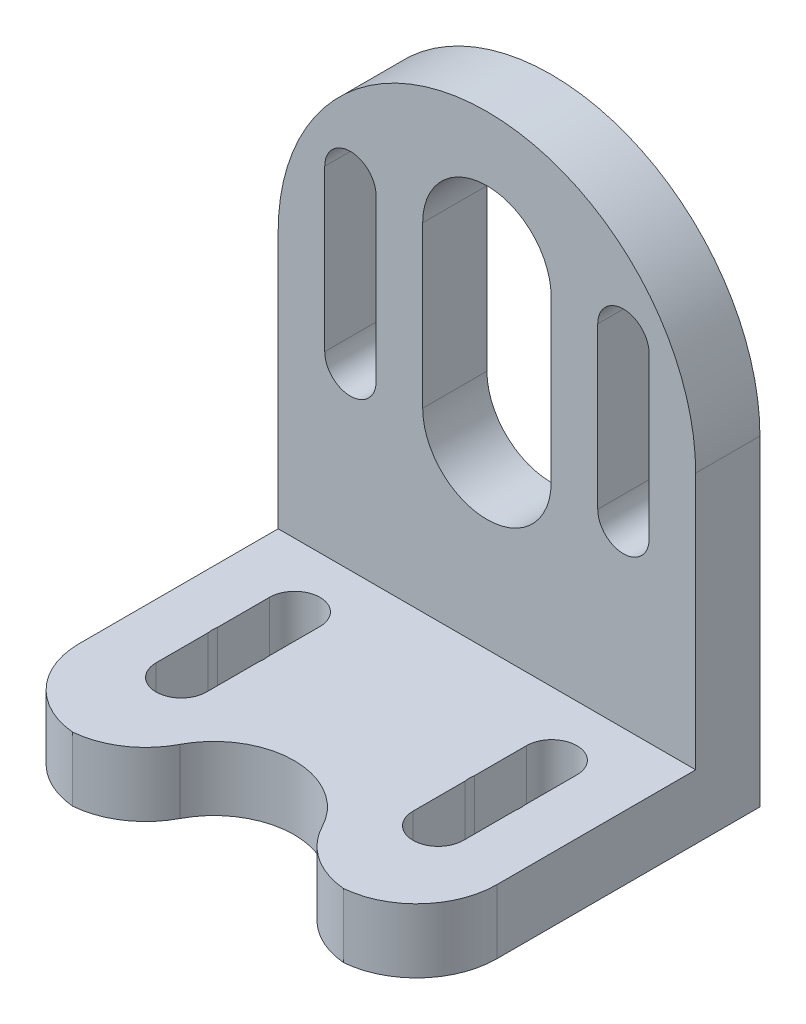
SolidWorks part; units mm, degrees
ref_plane "Front Plane" through (0, 0, 0) normal (0, 0, 1) x (1, 0, 0)
ref_plane "Top Plane" through (0, 0, 0) normal (0, 1, 0) x (1, 0, 0)
ref_plane "Right Plane" through (0, 0, 0) normal (1, 0, 0) x (0, 0, -1)
sketch "Sketch1" plane through (0, 0, 0) normal (0, 0, 1) x (1, 0, 0)
  line L0 (0, 23) -> (0, -10) construction
  line L1 (13, -10) -> (-13, -10)
  line L2 (13, -10) -> (13, 10)
  line L4 (-13, -10) -> (-13, 10)
  line L5 (13, -10) -> (-13, 10) construction
  line L6 (13, 10) -> (-13, -10) construction
  arc A0 (-13, 10) -> (13, 10) centre (0, 10) cw
  circle A1 centre (0, 10) radius 4
  circle A2 centre (-8.5, 10) radius 1.6
  circle A3 centre (8.5, 10) radius 1.6
  point P0 (0, 0)
  dimension "D3" = 13
  dimension "D4" = 8
  dimension "D5" = 3.2
  dimension "D1" = 26
  dimension "D2" = 20
  dimension "D6" = 8.5
extrude "Boss-Extrude1" add sketch "Sketch1" along normal blind 4
sketch "Sketch2" plane through (0, 0, 4) normal (0, 0, 1) x (1, 0, 0)
  line L0 (13, -10) -> (13, 10) construction
  line L1 (-13, -10) -> (13, -10)
  line L2 (-13, -10) -> (-13, -6)
  line L3 (-13, -6) -> (13, -6)
  line L4 (13, -10) -> (13, -6)
  dimension "D1" = 4
extrude "Boss-Extrude2" add sketch "Sketch2" along normal blind 33
sketch "Sketch3" plane through (0, -10, 0) normal (0, -1, 0) x (1, 0, 0)
  line L0 (0, 37) -> (0, 0) construction
  line L1 (-13, 37) -> (13, 37) construction
  line L2 (-13, 18.5) -> (13, 18.5) construction
  line L3 (-13, 37) -> (-13, 0) construction
  line L4 (13, 37) -> (13, 0) construction
  circle A0 centre (0, 21) radius 5
  circle A1 centre (-8, 25.5) radius 1.6
  circle A2 centre (8, 25.5) radius 1.6
  circle A3 centre (8, 11.5) radius 1.6
  circle A4 centre (-8, 11.5) radius 1.6
  dimension "D2" = 10
  dimension "D3" = 3.2
  dimension "D1" = 16
  dimension "D4" = 8
  dimension "D5" = 14
extrude "Cut-Extrude1" cut sketch "Sketch3" against normal blind 33
sketch "Sketch4" plane through (0, 0, 4) normal (0, 0, 1) x (1, 0, 0)
  line L0 (-8.5, 5) -> (-8.5, 15) construction
  line L1 (-10.1, 5) -> (-10.1, 15)
  line L2 (-6.9, 5) -> (-6.9, 15)
  line L3 (0, 23) -> (0, -0.4372) construction
  line L4 (8.5, 5) -> (8.5, 15) construction
  line L5 (10.1, 5) -> (10.1, 15)
  line L6 (6.9, 5) -> (6.9, 15)
  arc A0 (-10.1, 5) -> (-6.9, 5) centre (-8.5, 5) ccw
  arc A1 (-6.9, 15) -> (-10.1, 15) centre (-8.5, 15) ccw
  arc A2 (13, 10) -> (-13, 10) centre (0, 10) ccw construction
  arc A3 (10.1, 5) -> (6.9, 5) centre (8.5, 5) cw
  arc A4 (6.9, 15) -> (10.1, 15) centre (8.5, 15) cw
  point P2 (-8.5, 10)
  point P17 (8.5, 10)
  dimension "D1" = 1.6
  dimension "D2" = 10
extrude "Cut-Extrude2" cut sketch "Sketch4" against normal blind 33
sketch "Sketch5" plane through (0, 0, 4) normal (0, 0, 1) x (1, 0, 0)
  line L0 (-10.1, 15) -> (-10.1, 5) construction
  line L1 (6.9, 15) -> (6.9, 5) construction
  line L2 (4, 10) -> (-10.1, 10) construction
  circle A0 centre (-8.5, 10) radius 1.6
  circle A1 centre (8.5, 10) radius 1.6
  circle A2 centre (0, 10) radius 4 construction
  dimension "D1" = 3.2
  dimension "D2" = 3.2
sketch "Sketch6" plane through (0, -6, 0) normal (0, 1, 0) x (1, 0, 0)
  line L0 (8, -15.0323) -> (8, -7.9677) construction
  line L1 (6.4265, -15.0323) -> (6.4265, -7.9677)
  line L2 (9.5735, -15.0323) -> (9.5735, -7.9677)
  line L3 (0, -4) -> (0, -16) construction
  line L4 (4, -4) -> (-10.1, -4) construction
  line L5 (-8, -15.0323) -> (-8, -7.9677) construction
  line L6 (-6.4265, -15.0323) -> (-6.4265, -7.9677)
  line L7 (-9.5735, -15.0323) -> (-9.5735, -7.9677)
  arc A0 (6.4265, -15.0323) -> (9.5735, -15.0323) centre (8, -15.0323) ccw
  arc A1 (9.5735, -7.9677) -> (6.4265, -7.9677) centre (8, -7.9677) ccw
  circle A2 centre (0, -21) radius 5 construction
  arc A3 (-6.4265, -15.0323) -> (-9.5735, -15.0323) centre (-8, -15.0323) cw
  arc A4 (-9.5735, -7.9677) -> (-6.4265, -7.9677) centre (-8, -7.9677) cw
  point P2 (8, -11.5)
  point P17 (-8, -11.5)
extrude "Cut-Extrude3" cut sketch "Sketch6" against normal blind 5
sketch "Sketch7" plane through (0, -6, 0) normal (0, 1, 0) x (1, 0, 0)
  line L0 (13, -37) -> (13, -4) construction
  line L1 (-13, -37) -> (13, -37)
  line L2 (-13, -37) -> (-13, -21.3817)
  line L3 (-13, -21.3817) -> (13, -21.3817)
  line L4 (13, -37) -> (13, -21.3817)
extrude "Cut-Extrude4" cut sketch "Sketch7" against normal blind 5
fillet "Fillet1" radius 5 4 edges at (-13, -8, 21.3817) (13, -8, 21.3817) (4.9854, -8, 21.3817) (-4.9854, -8, 21.3817)
sketch "Sketch8" plane through (0, 0, 0) normal (0, 0, -1) x (-1, 0, 0)
  line L0 (0, 5) -> (0, 15) construction
  line L1 (-4, 5) -> (-4, 15)
  line L2 (4, 5) -> (4, 15)
  arc A0 (-4, 5) -> (4, 5) centre (0, 5) ccw
  arc A1 (4, 15) -> (-4, 15) centre (0, 15) ccw
  point P2 (0, 10)
  dimension "D1" = 4
  dimension "D2" = 10
extrude "Cut-Extrude5" cut sketch "Sketch8" against normal blind 10
